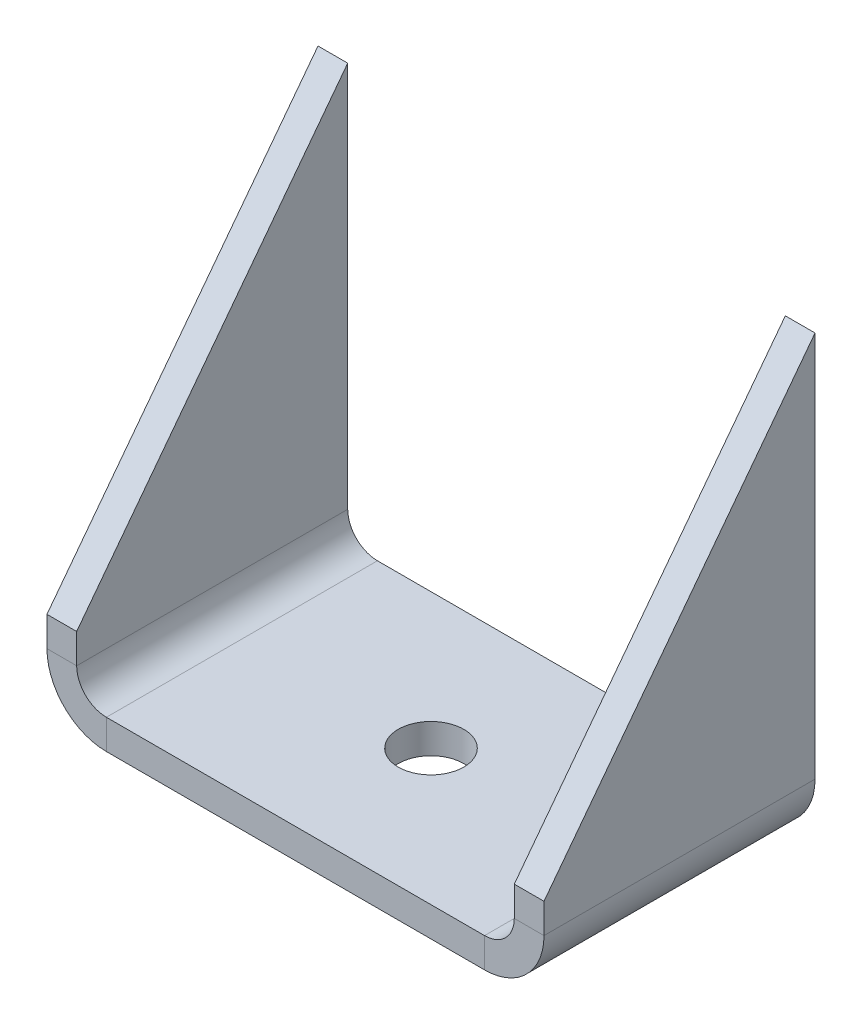
SolidWorks part; units mm, degrees
note: The reader was unsure of these and kept them because the rebuilt part matched: flange length of "Edge-Flange4".
material "6061-T6 (SS)"
ref_plane "X-Y Datum" through (0, 0, 0) normal (0, 0, 1) x (1, 0, 0)
ref_plane "X-Z Datum" through (0, 0, 0) normal (0, 1, 0) x (1, 0, 0)
ref_plane "Y-Z Datum" through (0, 0, 0) normal (1, 0, 0) x (0, 0, -1)
sketch "Sketch3" plane through (0, 0, 0) normal (0, 1, 0) x (1, 0, 0)
  line L1 (0, 0) -> (53.1, 0)
  line L2 (0, 0) -> (0, 28.956)
  line L3 (0, 28.956) -> (53.1, 28.956)
  line L4 (53.1, 0) -> (53.1, 28.956)
  dimension "D1" = 53.1
  dimension "D2" = 28.956
base flange "Base-Flange1" sketch "Sketch3" thickness 3.175 reverse thickness direction no parameters "D1"=3.175
edge flange "Edge-Flange4" sketch "Sketch23" flange profiles "Sketch23", "Sketch24" flange angle 90 flange length 44.45 flange position material inside bend radius 3.175 thickness 3.175 relief rectangular parameters "D1"=9.525, "D6"=10, "D8"=0.254
sketch "Sketch23" plane through (53.1, 0, 0) normal (1, 0, 0) x (0, 0, -1)
  line L0 (0, 0) -> (28.956, 0) construction
  line L1 (0, 0) -> (28.956, 0)
  line L4 (28.956, 44.45) -> (28.956, 0)
  line L5 (0, 0) -> (0, 6.35)
  line L6 (0, 6.35) -> (28.956, 44.45)
  dimension "D1" = 6.35
  dimension "D2" = 38.1
sketch "Sketch24" plane through (0, 0, 0) normal (-1, 0, 0) x (0, 0, 1)
  line L0 (-28.956, 0) -> (0, 0) construction
  line L1 (-28.956, 0) -> (0, 0)
  line L5 (0, 0) -> (0, 6.35)
  line L6 (0, 6.35) -> (-28.956, 44.45)
  line L7 (-28.956, 44.45) -> (-28.956, 0)
bend "EdgeBend4" bend radius 3.175 bend angle 90 parameters "D5"=1
bend "EdgeBend5" bend radius 3.175 bend angle 90 parameters "D5"=2
sketch "Sketch25" plane through (0, 0, 0) normal (0, 1, 0) x (1, 0, 0)
  line L0 (26.55, 28.956) -> (26.55, 0) construction
  line L2 (46.75, 28.956) -> (6.35, 28.956) construction
  line L3 (6.35, 0) -> (46.75, 0) construction
  point P6 (26.55, 14.478)
hole_wizard "M6 Clearance Hole1" positions "Sketch26" profile "Sketch27" hole size "M6" standard "ANSI Metric" end condition through all
sketch "Sketch26" plane through (0, 0, 0) normal (0, 1, 0) x (1, 0, 0)
  point P0 (26.55, 14.478)
sketch "Sketch27" plane through (26.55, 0, -14.478) normal (1, 0, 0) x (0, 0, 1)
  line L0 (0, 0) -> (0, 3.175)
  line L1 (0, 3.175) -> (3.5, 3.175)
  line L2 (3.5, 3.175) -> (3.5, 0)
  line L5 (3.5, 0) -> (0, 0)
  line L11 (0, -6.35) -> (0, 107.95) construction
  dimension "Thru Hole Dia." = 7
  dimension "Thru Hole Depth" = 3.175
sketch "Bend-Lines1" [suppressed] plane through (0, 0, 0) normal (0, 1, 0) x (1, 0, 0)
sketch "Bounding-Box1" [suppressed] plane through (0, 0, 0) normal (0, 1, 0) x (1, 0, 0)
sheet metal parameters "Sheet-Metal1" thickness 3.175 parameters "D1"=3.175
flat pattern "Flat-Pattern1" [suppressed]
sketch "Bend-Lines2" plane through (0, 0, 0) normal (0, 1, 0) x (1, 0, 0)
sketch3d "Bounding-Box2" [suppressed]
  line L0 (53.1, 28.956, 0) -> (0, 28.956, 0) construction
  line L1 (53.1, 0, 0) -> (0, 0, 0) construction
  line L2 (53.1, 28.956, 0) -> (53.1, 0, 0) construction
  line L3 (0, 28.956, 0) -> (0, 0, 0) construction
sheet metal parameters "Sheet-Metal5" thickness 3.175 parameters "D1"=3.175
flat pattern "Flat-Pattern1"
sketch "Bend-Lines2" plane through (0, 0, 0) normal (0, 1, 0) x (1, 0, 0)
  line L0 (2.6095, 28.956) -> (2.6095, 0) construction
  line L1 (50.4905, 0) -> (50.4905, 28.956) construction
  line L2 (2.6095, 28.956) -> (2.6095, 0) construction
  line L3 (50.4905, 0) -> (50.4905, 28.956) construction
sketch3d "Bounding-Box2" [suppressed]
  line L0 (95.5059, 28.956, 0) -> (-42.4059, 28.956, 0) construction
  line L1 (95.5059, 0, 0) -> (-42.4059, 0, 0) construction
  line L2 (95.5059, 28.956, 0) -> (95.5059, 0, 0) construction
  line L3 (-42.4059, 28.956, 0) -> (-42.4059, 0, 0) construction
bend of the flat pattern "Flatten-<EdgeBend4>1"
bend of the flat pattern "Flatten-<EdgeBend5>1"
sheet metal parameters "Sheet-Metal7" thickness 3.175 parameters "D1"=3.175
flat pattern "Flat-Pattern1"
sketch "Bend-Lines2" plane through (0, 0, 0) normal (0, 1, 0) x (1, 0, 0)
  line L0 (2.6095, 28.956) -> (2.6095, 0) construction
  line L1 (50.4905, 0) -> (50.4905, 28.956) construction
  line L2 (2.6095, 28.956) -> (2.6095, 0) construction
  line L3 (50.4905, 0) -> (50.4905, 28.956) construction
sketch3d "Bounding-Box2" [suppressed]
  line L0 (95.5059, 28.956, 0) -> (-42.4059, 28.956, 0) construction
  line L1 (95.5059, 0, 0) -> (-42.4059, 0, 0) construction
  line L2 (95.5059, 28.956, 0) -> (95.5059, 0, 0) construction
  line L3 (-42.4059, 28.956, 0) -> (-42.4059, 0, 0) construction
bend of the flat pattern "Flatten-<EdgeBend4>1"
bend of the flat pattern "Flatten-<EdgeBend5>1"
